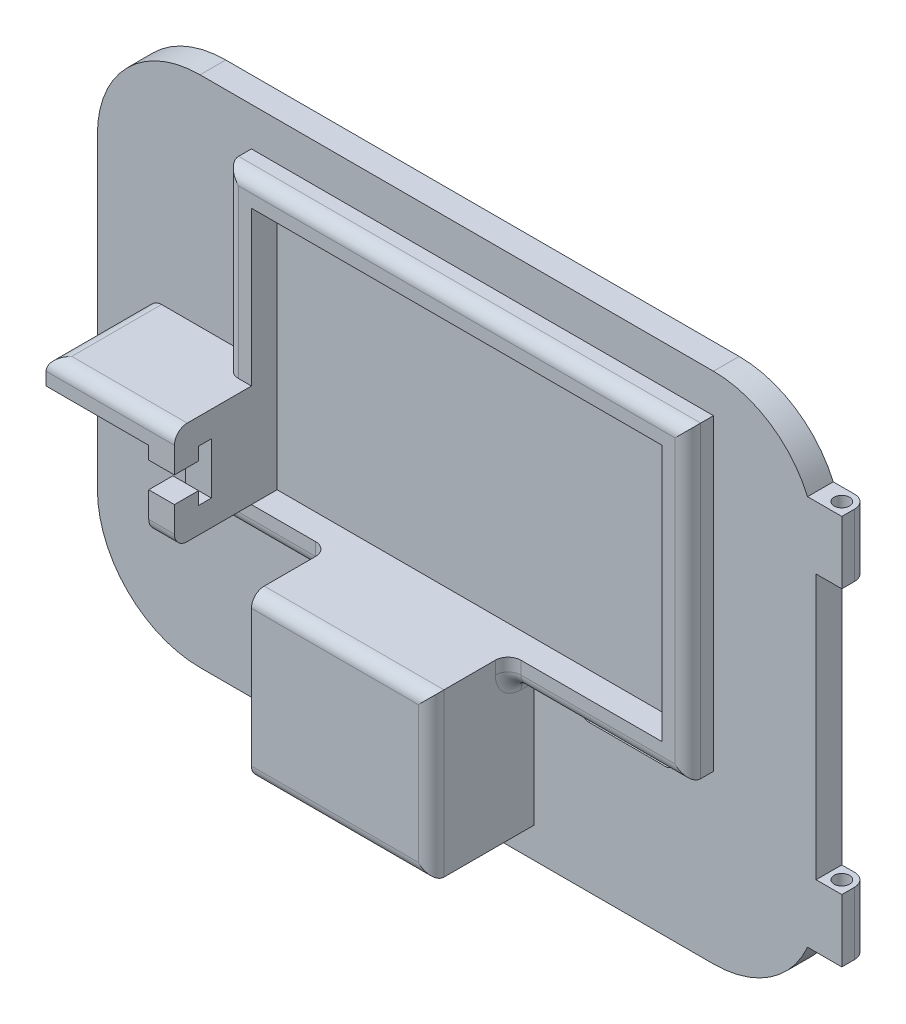
SolidWorks part; units mm, degrees
ref_plane "Front Plane" through (0, 0, 0) normal (0, 0, 1) x (1, 0, 0)
ref_plane "Top Plane" through (0, 0, 0) normal (0, 1, 0) x (1, 0, 0)
ref_plane "Right Plane" through (0, 0, 0) normal (1, 0, 0) x (0, 0, -1)
sketch "Sketch1" plane through (0, 0, 0) normal (0, 0, 1) x (1, 0, 0)
  line L0 (-63.5, 63.5) -> (63.5, 63.5)
  line L1 (63.5, -63.5) -> (-63.5, -63.5)
  line L2 (-88.9, -38.1) -> (-88.9, 38.1)
  line L3 (88.9, -38.1) -> (88.9, 38.1)
  arc A0 (-88.9, 38.1) -> (-63.5, 63.5) centre (-63.5, 38.1) cw
  arc A1 (-63.5, -63.5) -> (-88.9, -38.1) centre (-63.5, -38.1) cw
  arc A2 (63.5, -63.5) -> (88.9, -38.1) centre (63.5, -38.1) ccw
  arc A3 (88.9, 38.1) -> (63.5, 63.5) centre (63.5, 38.1) ccw
  dimension "D1" = 25.4
  dimension "D2" = 88.9
  dimension "D3" = 88.9
  dimension "D4" = 63.5
  dimension "D5" = 63.5
extrude "Boss-Extrude1" add sketch "Sketch1" against normal blind 6.35
sketch "Sketch3" plane through (0, 0, 0) normal (0, 0, 1) x (1, 0, 0)
  line L0 (63.5, 63.5) -> (88.9, 63.5) construction
  line L1 (88.9, 63.5) -> (95.25, 63.5) construction
  line L6 (95.25, 32.75) -> (95.25, 48.26)
  line L8 (95.25, 48.26) -> (86.7795, 48.26)
  line L9 (95.25, 63.5) -> (95.25, 32.75) construction
  line L10 (95.25, 32.75) -> (88.9, 32.75)
  line L11 (88.9, -38.1) -> (88.9, 38.1) construction
  line L12 (88.9, 32.75) -> (88.9, 38.1)
  arc A0 (88.9, 38.1) -> (86.7795, 48.26) centre (63.5, 38.1) ccw
  dimension "D5" = 25.4
  dimension "D1" = 25.4
  dimension "D2" = 6.35
  dimension "D3" = 30.75
  dimension "D4" = 15.24
extrude "Boss-Extrude2" add sketch "Sketch3" against normal up to surface (6.35 mm away) up to face at (0, 0, -6.35)
sketch "Sketch4" plane through (0, 48.26, 0) normal (0, 1, 0) x (1, 0, 0)
  line L0 (95.25, 3.175) -> (92.075, 3.175) construction
  line L1 (95.25, 6.35) -> (95.25, 0) construction
  circle A0 centre (92.075, 3.175) radius 1.905
  point P6 (93.98, 3.175)
  dimension "D1" = 3.81
  dimension "D2" = 1.27
extrude "Cut-Extrude2" cut sketch "Sketch4" against normal up to next
sketch "Sketch5" plane through (0, 0, 0) normal (0, 0, 1) x (1, 0, 0)
  line L0 (0, 0) -> (88.9402, 0)
mirror "Mirror1" about plane through (0, 0, 0) normal (0, 1, 0) of "Cut-Extrude2", "Boss-Extrude2"
sketch "Sketch7" plane through (0, 0, -6.35) normal (0, 0, -1) x (-1, 0, 0)
  line L0 (0, 0) -> (57.15, 0) construction
  point P4 (57.15, 0)
  dimension "D1" = 57.15
ref_plane "Plane1" through (-57.15, 0, -6.35) normal (-1, 0, 0) x (0, 0, 1)
sketch "Sketch8" plane through (-57.15, 0, -6.35) normal (-1, 0, 0) x (0, 0, 1)
  line L0 (0, 0) -> (0, 38.1) construction
  line L1 (0, 38.1) -> (0, 44.45)
  line L2 (-19.05, 25.4) -> (-19.05, -25.4)
  line L3 (0, 24.7494) -> (-24.0575, 24.7494) construction
  line L4 (-12.7, 25.4) -> (-12.7, 40.5526) construction
  line L5 (-19.05, 0) -> (-12.7, 0) construction
  line L6 (-12.7, -25.4) -> (-12.7, 25.4)
  line L7 (0, -38.1) -> (0, -44.45)
  arc A0 (0, 44.45) -> (-19.05, 25.4) centre (0, 25.4) ccw
  arc A1 (0, 38.1) -> (-12.7, 25.4) centre (0, 25.4) ccw
  arc A2 (0, -38.1) -> (-12.7, -25.4) centre (0, -25.4) cw
  arc A3 (0, -44.45) -> (-19.05, -25.4) centre (0, -25.4) cw
  dimension "D1" = 38.1
  dimension "D2" = 6.35
  dimension "D3" = 19.7006
  dimension "D4" = 12.7
extrude "Boss-Extrude3" add sketch "Sketch8" against normal blind 12.7
fillet "Fillet1" radius 6.35 1 edges at (-50.8, -44.45, -6.35)
fillet "Fillet2" radius 6.35 1 edges at (-57.15, -44.0467, -6.35)
fillet "Fillet3" radius 6.35 1 edges at (-44.45, -44.0467, -6.35)
fillet "Fillet4" radius 6.35 3 edges at (-50.8, 44.45, -6.35) (-44.45, 41.275, -6.35) (-57.15, 41.275, -6.35)
fillet "Fillet5" radius 3.175 2 edges at (95.25, -40.505, -6.35) (95.25, 40.505, -6.35)
sketch "Sketch9" plane through (0, 0, 0) normal (0, 0, 1) x (1, 0, 0)
  line L0 (88.9402, 0) -> (-88.9, 0) construction
  line L1 (-88.9, 38.1) -> (-88.9, -38.1) construction
  line L22 (57.15, 47.625) -> (-44.45, 47.625)
  line L23 (57.15, 47.625) -> (57.15, -15.875)
  line L24 (57.15, -15.875) -> (-44.45, -15.875)
  line L25 (-44.45, 47.625) -> (-44.45, -15.875)
  line L26 (-63.5, -63.5) -> (63.5, -63.5) construction
  line L28 (63.5, 53.975) -> (63.5, -22.225)
  line L29 (63.5, -22.225) -> (-50.8, -22.225)
  line L30 (-50.8, 53.975) -> (-50.8, -22.225)
  line L31 (63.5, 53.975) -> (-50.8, 53.975)
  dimension "D1" = 63.5
  dimension "D2" = 101.6
  dimension "D3" = 47.625
  dimension "D4" = 38.1
  dimension "D5" = 6.35
extrude "Boss-Extrude4" add sketch "Sketch9" along normal blind 6.35
sketch "Sketch10" plane through (0, 0, 0) normal (0, 0, 1) x (1, 0, 0)
  line L0 (-44.45, 47.625) -> (-44.45, 10.9459) construction
  line L1 (57.15, -15.875) -> (57.15, -25.527) construction
  line L2 (32.639, -25.527) -> (51.689, -25.527) construction
  line L3 (32.639, -23.9395) -> (51.689, -23.9395)
  line L4 (32.639, -27.1145) -> (51.689, -27.1145)
  line L5 (57.15, -25.527) -> (42.164, -25.527) construction
  arc A0 (32.639, -23.9395) -> (32.639, -27.1145) centre (32.639, -25.527) ccw
  arc A1 (51.689, -27.1145) -> (51.689, -23.9395) centre (51.689, -25.527) ccw
  point P6 (42.164, -25.527)
  point P11 (0, 0)
  dimension "D1" = 9.652
  dimension "D2" = 14.986
  dimension "D3" = 19.05
  dimension "D4" = 3.175
extrude "Cut-Extrude3" cut sketch "Sketch10" against normal up to next
sketch "Sketch14" plane through (0, 0, 0) normal (0, 0, 1) x (1, 0, 0)
  line L0 (12.7, -22.225) -> (12.7, -49.657)
  line L1 (-50.8, -22.225) -> (63.5, -22.225) construction
  line L2 (12.7, -49.657) -> (-25.4, -49.657)
  line L3 (63.5, -22.225) -> (63.5, 53.975) construction
  line L4 (19.05, -22.225) -> (19.05, -56.007)
  line L5 (19.05, -56.007) -> (-25.4, -56.007)
  line L6 (-25.4, -56.007) -> (-25.4, -49.657)
  line L7 (19.05, -15.875) -> (-25.4, -15.875)
  line L8 (-44.45, -15.875) -> (57.15, -15.875) construction
  line L9 (-25.4, -15.875) -> (-25.4, -22.225)
  line L10 (-25.4, -22.225) -> (12.7, -22.225)
  line L11 (19.05, -22.225) -> (19.05, -15.875)
  dimension "D1" = 38.1
  dimension "D2" = 27.432
  dimension "D3" = 50.8
  dimension "D4" = 6.35
extrude "Boss-Extrude7" add sketch "Sketch14" along normal blind 25.4
sketch "Sketch15" plane through (0, -49.657, 0) normal (0, 1, 0) x (1, 0, 0)
  line L0 (-25.4, -25.4) -> (-25.4, -19.05)
  line L1 (-25.4, -25.4) -> (-25.4, 0) construction
  line L2 (-25.4, -19.05) -> (12.7, -19.05)
  line L3 (12.7, -25.4) -> (12.7, 0) construction
  line L4 (12.7, -19.05) -> (12.7, -25.4)
  line L5 (12.7, -25.4) -> (-25.4, -25.4)
  dimension "D1" = 6.35
extrude "Boss-Extrude8" add sketch "Sketch15" along normal up to next
sketch "Sketch16" plane through (0, 0, 0) normal (0, 0, 1) x (1, 0, 0)
  line L0 (-50.8, 3.175) -> (-76.2, 3.175)
  line L1 (-50.8, 53.975) -> (-50.8, -22.225) construction
  line L2 (63.5, 53.975) -> (-50.8, 53.975) construction
  line L3 (-76.2, 9.525) -> (-76.2, 3.175)
  line L4 (-50.8, 9.525) -> (-44.45, 9.525)
  line L5 (-44.45, 47.625) -> (-44.45, -15.875) construction
  line L6 (-44.45, 9.525) -> (-44.45, -15.875)
  line L7 (-44.45, -15.875) -> (-50.8, -15.875)
  line L8 (-50.8, -15.875) -> (-50.8, 3.175)
  line L9 (-44.45, -15.875) -> (-25.4, -15.875) construction
  line L13 (-50.8, 9.525) -> (-76.2, 9.525)
  point P8 (-47.625, -15.875)
  dimension "D1" = 25.4
  dimension "D2" = 50.8
  dimension "D3" = 6.35
extrude "Boss-Extrude9" add sketch "Sketch16" along normal blind 25.4
sketch "Sketch17" plane through (-50.8, 0, 0) normal (-1, 0, 0) x (0, 0, 1)
  line L0 (0, 3.175) -> (16.256, 3.175) construction
  line L1 (0, 3.175) -> (25.4, 3.175) construction
  line L2 (16.256, 3.175) -> (16.256, -9.525)
  line L3 (16.256, -9.525) -> (19.431, -9.525)
  line L4 (19.431, -9.525) -> (19.431, 3.175)
  line L5 (19.431, 3.175) -> (16.256, 3.175)
  dimension "D1" = 16.256
  dimension "D2" = 12.7
  dimension "D3" = 3.175
extrude "Cut-Extrude4" cut sketch "Sketch17" against normal up to next
sketch "Sketch18" plane through (0, 0, 25.4) normal (0, 0, 1) x (1, 0, 0)
  line L0 (-50.8, 0) -> (-44.45, 0) construction
  line L1 (-44.45, -15.875) -> (-44.45, 9.525) construction
  line L4 (-50.8, 3.175) -> (-50.8, -15.875) construction
  line L5 (-44.45, 0) -> (-50.8, 0)
  line L6 (-44.45, 0) -> (-44.45, -6.35)
  line L7 (-44.45, -6.35) -> (-50.8, -6.35)
  line L8 (-50.8, 0) -> (-50.8, -6.35)
  line L9 (-44.45, 0) -> (-50.8, -6.35) construction
  line L10 (-44.45, -6.35) -> (-50.8, 0) construction
  line L11 (-44.45, 47.625) -> (-44.45, -15.875) construction
  line L12 (-76.2, 3.175) -> (-50.8, 3.175) construction
  dimension "D1" = 6.35
  dimension "D2" = 3.175
extrude "Cut-Extrude5" cut sketch "Sketch18" against normal up to next
fillet "Fillet6" radius 3.175 15 edges at (19.05, -35.941, 25.4) (-3.175, -15.875, 25.4) (-3.175, -56.007, 25.4) (-25.4, -22.225, 12.7) (19.05, -22.225, 3.175) (-50.8, 31.75, 6.35) (-50.8, -19.05, 6.35) (41.275, -22.225, 6.35) (63.5, 15.875, 6.35) (6.35, 53.975, 6.35) (-25.4, -19.05, 6.35) (19.05, -19.05, 6.35) (-76.2, 9.525, 12.7) (-60.325, 9.525, 25.4) (-47.625, -15.875, 25.4)
